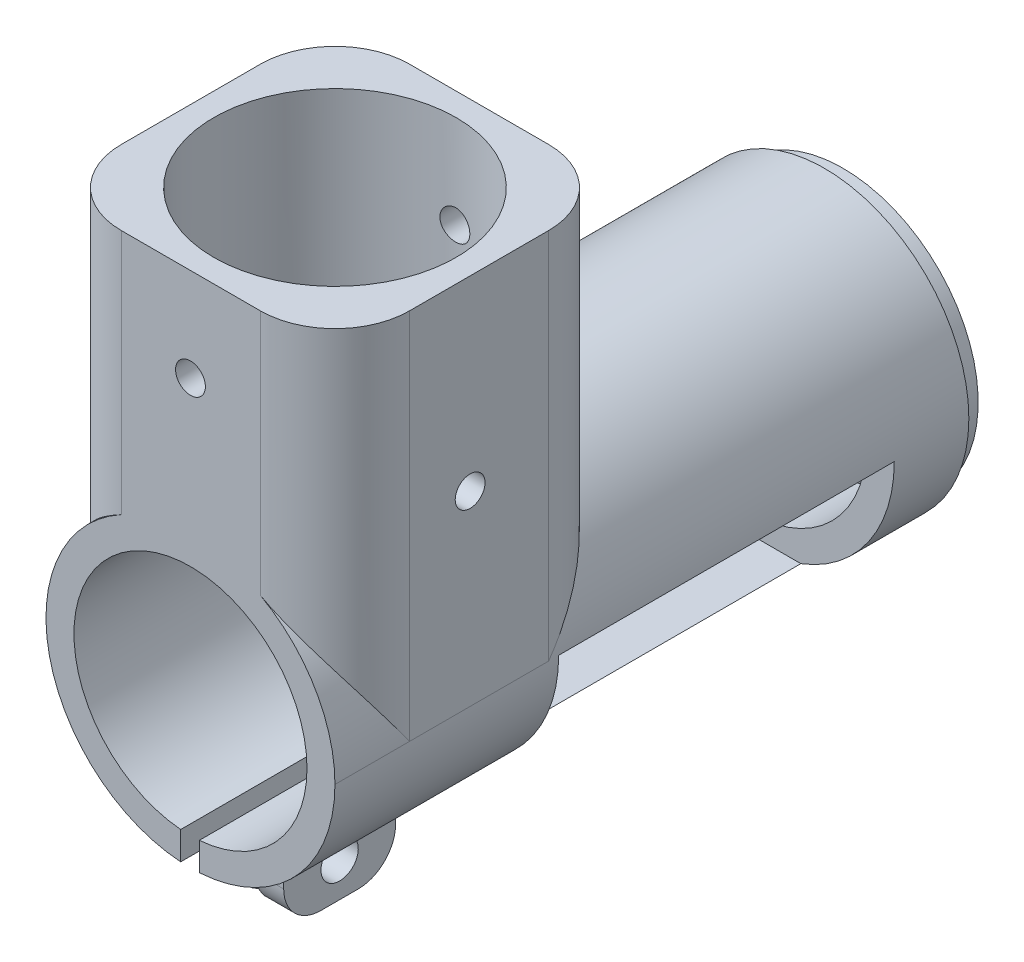
SolidWorks part; units mm, degrees
ref_plane "Front" through (0, 0, 0) normal (0, 0, 1) x (1, 0, 0)
ref_plane "Top" through (0, 0, 0) normal (0, 1, 0) x (1, 0, 0)
ref_plane "Right" through (0, 0, 0) normal (1, 0, 0) x (0, 0, -1)
sketch "Эскиз1" plane through (0, 0, 0) normal (0, 0, 1) x (1, 0, 0)
  circle A0 centre (0, 0) radius 12.5
  circle A1 centre (0, 0) radius 15.5
extrude "Бобышка-Вытянуть1" add sketch "Эскиз1" along normal blind 68
sketch "Эскиз2" plane through (0, 0, 0) normal (0, 0, -1) x (-1, 0, 0)
  circle A0 centre (0, 0) radius 14.5
  circle A2 centre (8.5, 0) radius 1.6
  circle A3 centre (-8.5, 0) radius 1.6
  circle A4 centre (0, 0) radius 5
extrude "Бобышка-Вытянуть2" add sketch "Эскиз2" along normal blind 2
sketch "Эскиз3" plane through (0, 0, 0) normal (0, 1, 0) x (1, 0, 0)
  line L2 (-7.4174, -37.0826) -> (7.5, -37.0826)
  line L3 (-15.4174, -45.0826) -> (-15.4174, -60)
  line L4 (-7.4174, -68) -> (7.5, -68)
  line L5 (15.5, -45.0826) -> (15.5, -60)
  line L6 (-15.4174, -37.0826) -> (15.5, -68) construction
  line L7 (-15.4174, -68) -> (15.5, -37.0826) construction
  circle A3 centre (0.0413, -52.5413) radius 13
  arc A4 (-15.4174, -60) -> (-7.4174, -68) centre (-7.4174, -60) ccw
  arc A5 (7.5, -68) -> (15.5, -60) centre (7.5, -60) ccw
  arc A6 (7.5, -37.0826) -> (15.5, -45.0826) centre (7.5, -45.0826) cw
  arc A7 (-7.4174, -37.0826) -> (-15.4174, -45.0826) centre (-7.4174, -45.0826) ccw
  dimension "D1" = 8
extrude "Бобышка-Вытянуть3" add sketch "Эскиз3" along normal blind 40
sketch "Эскиз4" plane through (0, 0, 68) normal (0, 0, 1) x (1, 0, 0)
  circle A0 centre (0, 0) radius 12.5
extrude "Вырез-Вытянуть1" cut sketch "Эскиз4" against normal blind 40
sketch "Эскиз5" plane through (0, 0, 0) normal (0, 0, 1) x (1, 0, 0)
  circle A1 centre (0, 30) radius 1.6
extrude "Вырез-Вытянуть4" cut sketch "Эскиз5" along normal through all
sketch "Эскиз6" plane through (0, 0, 0) normal (1, 0, 0) x (0, 0, -1)
  circle A1 centre (-53.5, 20) radius 1.6
extrude "Вырез-Вытянуть5" cut sketch "Эскиз6" against normal blind 40 and the other way blind 40
sketch "Эскиз7" plane through (0, 0, 0) normal (1, 0, 0) x (0, 0, -1)
  line L1 (-8, -14.5) -> (-44, -14.5)
  line L2 (-8, -14.5) -> (-8, 0)
  line L3 (-8, 0) -> (-44, 0)
  line L4 (-44, -14.5) -> (-44, 0)
extrude "Вырез-Вытянуть6" cut sketch "Эскиз7" against normal through all and the other way through all
sketch "Эскиз8" plane through (0, 0, 68) normal (0, 0, 1) x (1, 0, 0)
  line L1 (-1.0471, -10.2054) -> (0.9529, -10.2054)
  line L2 (-1.0471, -10.2054) -> (-1.0471, -20.7945)
  line L3 (-1.0471, -20.7945) -> (0.9529, -20.7945)
  line L4 (0.9529, -10.2054) -> (0.9529, -20.7945)
  line L5 (-1.0471, -10.2054) -> (0.9529, -20.7945) construction
  line L6 (-1.0471, -20.7945) -> (0.9529, -10.2054) construction
  arc A0 (-7.4174, 13.61) -> (7.5, 13.5647) centre (0, 0) ccw construction
  point P0 (-0.0471, -15.4999)
extrude "Вырез-Вытянуть7" cut sketch "Эскиз8" against normal blind 40
ref_plane "Плоскость1" through (0, 0, 56) normal (0, 0, -1) x (-1, 0, 0)
sketch "Эскиз9" plane through (0, 0, 56) normal (0, 0, -1) x (-1, 0, 0)
  line L5 (1.0471, -12.4561) -> (5, -12.4561)
  line L6 (1.0471, -12.4561) -> (1.0471, -22.4599)
  line L7 (1.0471, -22.4599) -> (5, -22.4599)
  line L8 (5, -12.4561) -> (5, -22.4599)
  line L9 (-0.9529, -12.4636) -> (-4, -12.4636)
  line L10 (-0.9529, -12.4636) -> (-0.9529, -22.4599)
  line L11 (-0.9529, -22.4599) -> (-4, -22.4599)
  line L12 (-4, -12.4636) -> (-4, -22.4599)
extrude "Бобышка-Вытянуть4" add sketch "Эскиз9" along normal blind 6 and the other way blind 6
sketch "Эскиз10" plane through (4, 0, 0) normal (1, 0, 0) x (0, 0, -1)
  line L0 (-62, -14.975) -> (-50, -22.4599) construction
  circle A0 centre (-56, -18.7175) radius 2
extrude "Вырез-Вытянуть8" cut sketch "Эскиз10" against normal through all
sketch "Эскиз11" plane through (-5, 0, 0) normal (-1, 0, 0) x (0, 0, 1)
  line L1 (60.0415, -18.7175) -> (58.0207, -15.2175)
  line L2 (58.0207, -15.2175) -> (53.9793, -15.2175)
  line L3 (53.9793, -15.2175) -> (51.9585, -18.7175)
  line L4 (51.9585, -18.7175) -> (53.9793, -22.2175)
  line L5 (53.9793, -22.2175) -> (58.0207, -22.2175)
  line L6 (58.0207, -22.2175) -> (60.0415, -18.7175)
  circle A0 centre (56, -18.7175) radius 3.5 construction
extrude "Вырез-Вытянуть9" cut sketch "Эскиз11" against normal blind 2
fillet "Скругление1" radius 4 4 edges at (-3.0235, -22.4599, 50) (-3.0235, -22.4599, 62) (2.4765, -22.4599, 62) (2.4765, -22.4599, 50)
sketch "Эскиз12" plane through (0, 40, 0) normal (0, 1, 0) x (1, 0, 0)
  line L0 (0.0413, -65.5413) -> (0.0413, -68) construction
  line L1 (-7.4174, -68) -> (7.5, -68) construction
  circle A0 centre (0.0413, -52.5413) radius 13 construction
